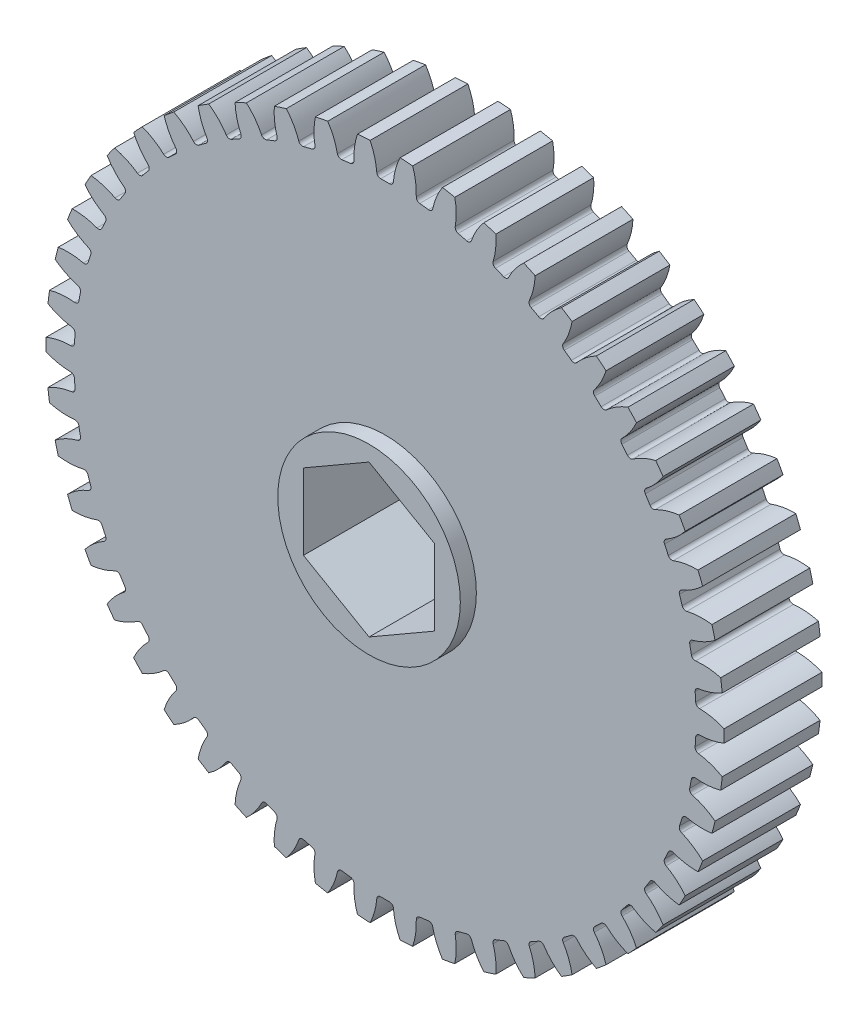
SolidWorks part; units mm, degrees
material "7075-T6 (SN)"
ref_plane "Alzado" through (0, 0, 0) normal (0, 0, 1) x (1, 0, 0)
ref_plane "Planta" through (0, 0, 0) normal (0, 1, 0) x (1, 0, 0)
ref_plane "Vista lateral" through (0, 0, 0) normal (1, 0, 0) x (0, 0, -1)
sketch "Croquis1" plane through (0, 0, 0) normal (0, 0, 1) x (1, 0, 0)
  circle A0 centre (0, 0) radius 31.75 construction
  circle A1 centre (0, 0) radius 33.02
  dimension "D" = 63.5
  dimension "OD" = 66.04
extrude "Saliente-Extruir1" add sketch "Croquis1" along normal mid plane 9.525
sketch "Croquis2" plane through (0, 0, 0) normal (0, 0, 1) x (1, 0, 0)
  line L0 (0, 0) -> (0, 33.02) construction
  line L1 (0, 0) -> (4.1385, 32.7596) construction
  line L2 (0, 0) -> (2.0733, 32.9548) construction
  line L3 (-0.7916, 30.2703) -> (0, 0) construction
  line L4 (-0.9973, 31.7343) -> (0.9973, 31.7343) construction
  line L5 (0.9973, 31.7343) -> (2.9879, 31.6091) construction
  line L6 (-1.3229, 32.9935) -> (0, 27.8781) construction
  circle A0 centre (0, 0) radius 33.02 construction
  arc A2 (0.7916, 30.2703) -> (-0.7916, 30.2703) centre (0, 0) ccw
  circle A5 centre (0, 0) radius 31.75 construction
  arc A6 (-1.4628, 32.9876) -> (-0.7916, 30.2703) centre (-7.3184, 30.0996) cw
  arc A7 (1.4628, 32.9876) -> (0.7916, 30.2703) centre (7.3184, 30.0996) ccw
  arc A8 (1.4628, 32.9876) -> (-1.4628, 32.9876) centre (0, 0) ccw
  dimension "D1" = 7.2
  dimension "D2" = 3.6
  dimension "B" = 1.4694
  dimension "Pressure Angle" = 14.5
extrude "Cortar-Extruir1" cut sketch "Croquis2" against normal through all both and the other way through all
fillet "Redondeo1" radius 0.381 2 edges at (0.7916, 30.2703, 0) (-0.7916, 30.2703, 0)
pattern_circular "MatrizC1" count 50 over 360 about axis through (0, 0, 4.7625) along (0, 0, -1) of "Cortar-Extruir1", "Redondeo1"
sketch "Croquis3" plane through (0, 0, 0) normal (0, 0, 1) x (1, 0, 0)
  circle A0 centre (0, 0) radius 8.89
  dimension "sp" = 17.78
extrude "Saliente-Extruir2" add sketch "Croquis3" along normal mid plane 12.6492
sketch "Croquis4" plane through (0, 0, 0) normal (0, 0, 1) x (1, 0, 0)
  line L0 (6.3881, 3.6882) -> (0, 7.3763)
  line L1 (0, 7.3323) -> (-6.35, 3.6662)
  line L2 (-6.35, 3.6662) -> (-6.35, -3.6662)
  line L3 (-6.35, -3.6662) -> (0, -7.3323)
  line L4 (0, -7.3323) -> (6.35, -3.6662)
  line L5 (6.35, -3.6662) -> (6.35, 3.6662)
  line L6 (6.35, 3.6662) -> (0, 7.3323)
  line L7 (0, 7.3763) -> (-6.3881, 3.6882)
  line L8 (-6.3881, 3.6882) -> (-6.3881, -3.6882)
  line L9 (-6.3881, -3.6882) -> (0, -7.3763)
  line L10 (0, -7.3763) -> (6.3881, -3.6882)
  line L11 (6.3881, -3.6882) -> (6.3881, 3.6882)
  circle A0 centre (0, 0) radius 6.35 construction
  dimension "D1" = 12.7
  dimension "D2" = 0.0381
extrude "Cortar-Extruir2" cut sketch "Croquis4" against normal through all both and the other way through all contours L7 L8 L9 L10 L11 L0
sketch "Croquis5" [suppressed] plane through (0, 0, 0) normal (0, 0, 1) x (1, 0, 0)
  circle A1 centre (0, 0) radius 21.8948
  circle A3 centre (0, 0) radius 26.67 construction
  circle A4 centre (0, 0) radius 8.89 construction
  circle A5 centre (0, 0) radius 8.89
  dimension "D1" = 4.7752
extrude "Cortar-Extruir3" [suppressed] cut sketch "Croquis5" along normal through all from offset 1.143
fillet "Redondeo2" [suppressed] radius 3.175
mirror "Simetría1" [suppressed] about plane through (0, 0, 0) normal (0, 0, 1)
other "PropertyManager" [suppressed]
equation "\"Number of teeth\" = 50"
equation "\"Diametral Pitch\"= 20"
equation "\"Pressure Angle\"= 14.5"
equation "\"D@Croquis1\"=\"Number of teeth\"/\"Diametral Pitch\""
equation "\"OD@Croquis1\"=(\"Number of teeth\"+2) /\"Diametral Pitch\""
equation "\"D2@Croquis2\"=(360 / \"Number of teeth\")/ 2."
equation "\"D1@Croquis2\"=360 / \"Number of teeth\""
equation "\"B@Croquis2\"=1.157 / \"Diametral Pitch\""
equation "\"Pressure Angle@Croquis2\" = \"Pressure Angle\""
equation "\"D1@Redondeo1\"=(pi / \"Diametral Pitch\") * .0955"
equation "\"D1@MatrizC1\"=\"Number of teeth\""
equation "\"Tt@Saliente-Extruir1\"=if( \"Number of teeth\"=>30,0.375,0.475)"
